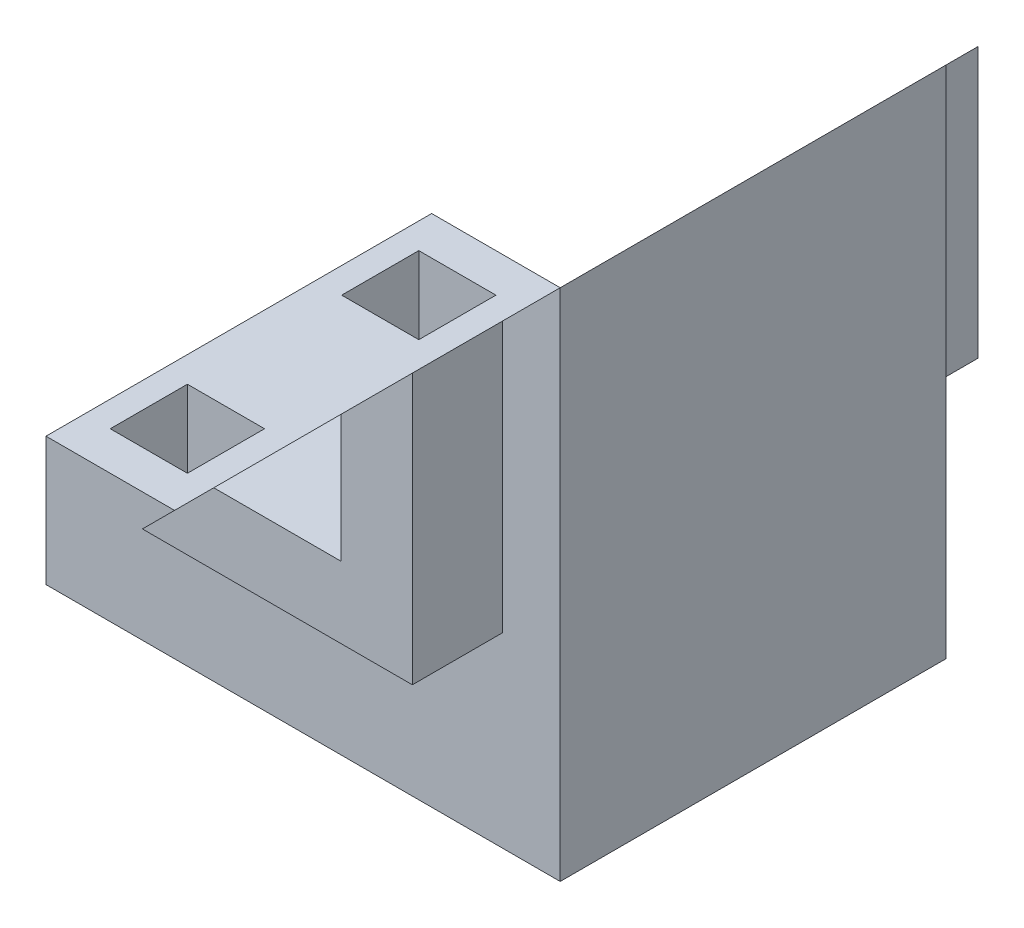
SolidWorks part; units mm, degrees
ref_plane "Спереди" through (0, 0, 0) normal (0, 0, 1) x (1, 0, 0)
ref_plane "Сверху" through (0, 0, 0) normal (0, 1, 0) x (1, 0, 0)
ref_plane "Справа" through (0, 0, 0) normal (1, 0, 0) x (0, 0, -1)
sketch "Эскиз1" plane through (0, 0, 0) normal (0, 0, 1) x (1, 0, 0)
  line L0 (-20, -10) -> (-10, -10)
  line L1 (-20, -20) -> (20, -20)
  line L2 (-20, -20) -> (-20, 20)
  line L3 (-20, 20) -> (20, 20)
  line L4 (20, -20) -> (20, 20)
  line L5 (-20, -20) -> (20, 20) construction
  line L6 (-20, 20) -> (20, -20) construction
  line L7 (-10, -10) -> (20, 20)
  line L8 (0.0503, 0.0503) -> (9.9497, 0.0503)
  line L9 (-5.5, -5.5) -> (15.5, -5.5)
  line L10 (-5.5, -5.5) -> (-5.5, 15.5)
  line L11 (-5.5, 15.5) -> (15.5, 15.5)
  line L12 (15.5, -5.5) -> (15.5, 15.5)
  line L13 (-5.5, -5.5) -> (15.5, 15.5) construction
  line L14 (-5.5, 15.5) -> (15.5, -5.5) construction
  line L15 (9.9497, 0.0503) -> (9.9497, 9.9497)
  circle A0 centre (5, 5) radius 7 construction
  point P0 (0, 0)
  dimension "D4" = 14
  dimension "D1" = 40
  dimension "D2" = 40
  dimension "D3" = 10
  dimension "D5" = 21
extrude "Бобышка-Вытянуть3" add sketch "Эскиз1" along normal blind 15 and the other way blind 15 contours L12 L9 L7 L0 L2 L1 L4 region at (4.1712, -10.0568, 0)
extrude "Бобышка-Вытянуть4" add sketch "Эскиз1<6>" along normal blind 22 and the other way blind 22 contours A0 L7 L9 L12 region at (-2.5149, -2.9349, 0)
sketch "Эскиз1<6>" plane through (0, 0, 0) normal (0, 0, 1) x (1, 0, 0) same geometry as "Эскиз1"
sketch "Эскиз2" plane through (0, -10, 0) normal (0, 1, 0) x (1, 0, 0)
  line L0 (-15, -15) -> (-15, 15) construction
  line L1 (-20, -15) -> (-10, -15) construction
  line L2 (-20, 15) -> (-10, 15) construction
  line L4 (-18, -6) -> (-12, -6)
  line L5 (-18, -6) -> (-18, -12)
  line L6 (-18, -12) -> (-12, -12)
  line L7 (-12, -6) -> (-12, -12)
  line L8 (-18, -6) -> (-12, -12) construction
  line L9 (-18, -12) -> (-12, -6) construction
  point P6 (-15, -9)
  dimension "D1" = 6
  dimension "D2" = 3
extrude "Вырез-Вытянуть2" cut sketch "Эскиз2" against normal through all
mirror "Зеркальное отражение1" about plane through (0, 0, 0) normal (0, 0, 1) of "Вырез-Вытянуть2"
